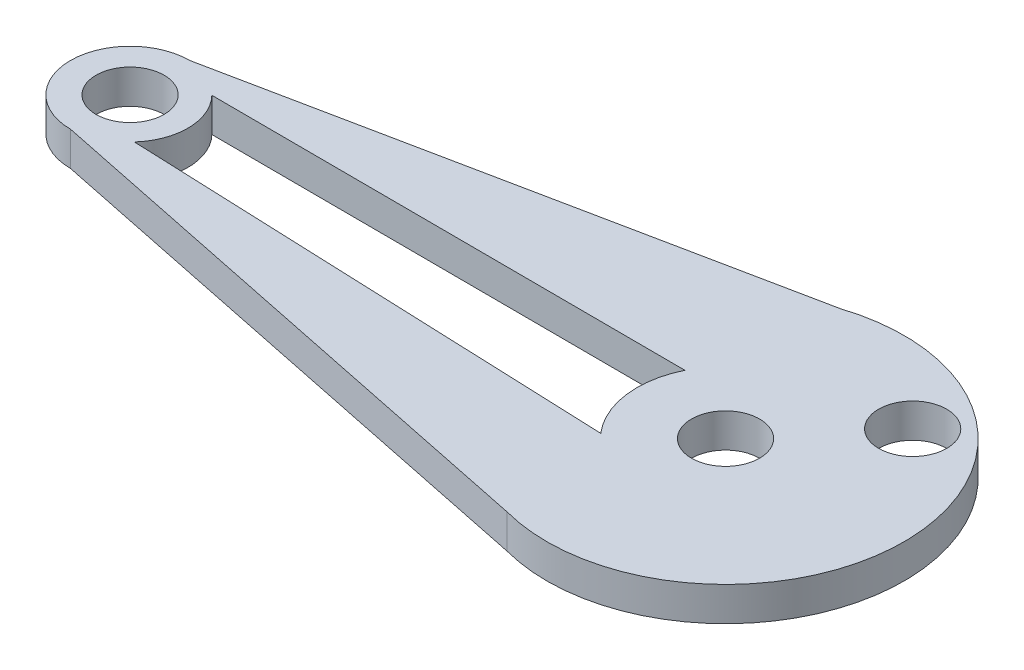
SolidWorks part; units mm, degrees
ref_plane "Front Plane" through (0, 0, 0) normal (0, 0, 1) x (1, 0, 0)
ref_plane "Top Plane" through (0, 0, 0) normal (0, 1, 0) x (1, 0, 0)
ref_plane "Right Plane" through (0, 0, 0) normal (1, 0, 0) x (0, 0, -1)
sketch "Sketch1" plane through (0, 0, 0) normal (0, 1, 0) x (1, 0, 0)
  line L0 (-51.6302, -6.0027) -> (-19.8587, 0.4886)
  line L1 (-51.6302, -13.0027) -> (-19.311, -19.6547)
  line L2 (-51.6302, -9.5027) -> (-16.6302, -9.5027) construction
  line L3 (-49.202, -7.1228) -> (-21.302, -7.2194)
  line L4 (-49.102, -11.7762) -> (-20.5646, -12.9027)
  arc A0 (-51.6302, -6.0027) -> (-51.6302, -13.0027) centre (-51.6302, -9.5027) ccw
  circle A1 centre (-16.6302, -9.5027) radius 2
  arc A2 (-19.311, -19.6547) -> (-19.8587, 0.4886) centre (-16.6302, -9.5027) ccw
  circle A3 centre (-51.6302, -9.5027) radius 2
  arc A4 (-49.102, -11.7762) -> (-49.202, -7.1228) centre (-51.6302, -9.5027) ccw
  arc A5 (-21.302, -7.2194) -> (-20.5646, -12.9027) centre (-16.6302, -9.5027) ccw
  circle A6 centre (-11.6302, -3.5027) radius 2
  dimension "D1" = 7
  dimension "D2" = 21
  dimension "D3" = 4
  dimension "D5" = 4
  dimension "D6" = 6.8
  dimension "D7" = 10.4
  dimension "D10" = 4
  dimension "D4" = 35
  dimension "D8" = 5
  dimension "D9" = 6
extrude "Boss-Extrude1" add sketch "Sketch1" along normal blind 2
